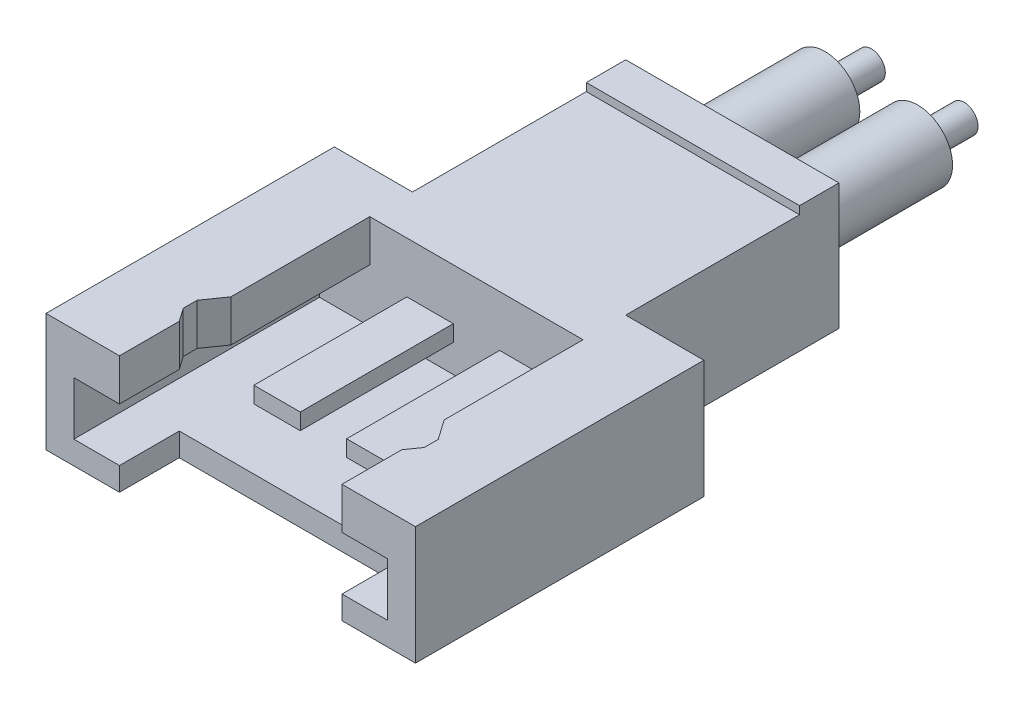
SolidWorks part; units mm, degrees
ref_plane "Front Plane" through (0, 0, 0) normal (0, 0, 1) x (1, 0, 0)
ref_plane "Top Plane" through (0, 0, 0) normal (0, 1, 0) x (1, 0, 0)
ref_plane "Right Plane" through (0, 0, 0) normal (1, 0, 0) x (0, 0, -1)
sketch "Sketch1" plane through (0, 0, 0) normal (0, 0, 1) x (1, 0, 0)
  line L1 (-2.3, 1.275) -> (2.3, 1.275)
  line L2 (-2.3, 1.275) -> (-2.3, -1.275)
  line L3 (-2.3, -1.275) -> (2.3, -1.275)
  line L4 (2.3, 1.275) -> (2.3, -1.275)
  line L5 (-2.3, 1.275) -> (2.3, -1.275) construction
  line L6 (-2.3, -1.275) -> (2.3, 1.275) construction
  point P0 (0, 0)
  dimension "D1" = 4.6
  dimension "D2" = 2.55
extrude "Boss-Extrude1" add sketch "Sketch1" along normal blind 4.6
sketch "Sketch2" plane through (0, 0, 4.6) normal (0, 0, 1) x (1, 0, 0)
  line L0 (2.3, 1.275) -> (-2.3, 1.275) construction
  line L1 (-3.985, 1.275) -> (3.985, 1.275)
  line L2 (-3.985, 1.275) -> (-3.985, -1.275)
  line L3 (-3.985, -1.275) -> (3.985, -1.275)
  line L4 (3.985, 1.275) -> (3.985, -1.275)
  line L5 (-3.985, 1.275) -> (3.985, -1.275) construction
  line L6 (-3.985, -1.275) -> (3.985, 1.275) construction
  point P0 (0, 0)
  dimension "D1" = 7.97
extrude "Boss-Extrude2" add sketch "Sketch2" along normal blind 6.22
sketch "Sketch3" plane through (0, 1.275, 0) normal (0, 1, 0) x (1, 0, 0)
  line L0 (2.3, -4.6) -> (2.3, 0) construction
  line L1 (-2.3, 0) -> (2.3, 0)
  line L2 (-2.3, 0) -> (-2.3, -0.85)
  line L3 (-2.3, -0.85) -> (2.3, -0.85)
  line L4 (2.3, 0) -> (2.3, -0.85)
  dimension "D1" = 0.85
extrude "Boss-Extrude3" add sketch "Sketch3" along normal offset from surface (0.17 mm away) 2.72 up to face at (0, -1.275, 5.005)
sketch "Sketch4" plane through (0, 0, 10.82) normal (0, 0, 1) x (1, 0, 0)
  line L0 (-3.985, -1.275) -> (3.985, -1.275) construction
  line L1 (-2.4, 1.275) -> (2.4, 1.275)
  line L2 (-2.4, 1.275) -> (-2.4, -1.275)
  line L3 (-2.4, -1.275) -> (2.4, -1.275)
  line L4 (2.4, 1.275) -> (2.4, -1.275)
  line L5 (-2.4, 1.275) -> (2.4, -1.275) construction
  line L6 (-2.4, -1.275) -> (2.4, 1.275) construction
  point P0 (0, 0)
  dimension "D1" = 4.8
extrude "Cut-Extrude1" cut sketch "Sketch4" against normal blind 1.29
sketch "Sketch5" plane through (0, 0, 10.82) normal (0, 0, 1) x (1, 0, 0)
  line L0 (0, 1.275) -> (0, -1.275) construction
  line L1 (-2.3, 1.275) -> (2.3, 1.275) construction
  line L2 (-2.4, -1.275) -> (2.4, -1.275) construction
  line L3 (-3.985, -1.275) -> (-2.4, -1.275) construction
  line L4 (-3.385, 0.375) -> (3.385, 0.375)
  line L5 (-3.385, 0.375) -> (-3.385, -0.775)
  line L6 (-3.385, -0.775) -> (3.385, -0.775)
  line L7 (3.385, 0.375) -> (3.385, -0.775)
  line L8 (-3.385, 0.375) -> (3.385, -0.775) construction
  line L9 (-3.385, -0.775) -> (3.385, 0.375) construction
  line L10 (-3.985, 1.275) -> (-3.985, -1.275) construction
  line L11 (-2.4, 1.275) -> (-3.985, 1.275) construction
  point P6 (0, -0.2)
  dimension "D1" = 0.5
  dimension "D2" = 0.6
  dimension "D3" = 0.9
extrude "Cut-Extrude2" cut sketch "Sketch5" against normal blind 5.3
sketch "Sketch6" plane through (0, 1.275, 0) normal (0, 1, 0) x (1, 0, 0)
  line L0 (0, -0.85) -> (0, -9.53) construction
  line L1 (-2.3, -0.85) -> (2.3, -0.85) construction
  line L2 (2.4, -9.53) -> (-2.4, -9.53) construction
  line L3 (-3.385, -5.52) -> (3.385, -5.52) construction
  line L4 (2.3, -5.52) -> (-2.3, -5.52)
  line L5 (2.3, -5.52) -> (2.3, -9.53)
  line L6 (2.3, -9.53) -> (-2.3, -9.53)
  line L7 (-2.3, -5.52) -> (-2.3, -9.53)
  line L8 (2.3, -5.52) -> (-2.3, -9.53) construction
  line L9 (2.3, -9.53) -> (-2.3, -5.52) construction
  line L10 (-2.4, -9.53) -> (-2.6, -9.2444)
  line L11 (-2.6, -9.2444) -> (-2.6, -8.9444)
  line L12 (-2.6, -8.9444) -> (-2.3, -8.5159)
  line L13 (-2.6, -9.0944) -> (-2.3, -9.0944) construction
  line L14 (-2.4, -9.53) -> (-2.3, -9.53)
  line L15 (2.6, -8.9444) -> (2.3, -8.5159)
  line L16 (2.6, -9.2444) -> (2.6, -8.9444)
  line L17 (2.4, -9.53) -> (2.6, -9.2444)
  line L18 (2.4, -9.53) -> (2.3, -9.53)
  point P6 (0, -7.525)
  line M3 (-2.4, -9.53) -> (2.4, -9.53)
  dimension "D1" = 4.6
  dimension "D2" = 0.3
  dimension "D3" = 145
  dimension "D4" = 0.3
extrude "Cut-Extrude3" cut sketch "Sketch6" against normal up to next contours L4 L7 L5 M3 | L12 L11 L10 L7 M3 | L17 L16 L15 L5 M3 region at (0, 1.275, 7.525) region at (2.4235, 1.275, 9.078) region at (-2.4235, 1.275, 9.078)
sketch "Sketch7" plane through (0, 0, 5.52) normal (0, 0, 1) x (1, 0, 0)
  line L0 (-3.985, 0) -> (3.985, 0) construction
  line L1 (-3.985, 1.275) -> (-3.985, -1.275) construction
  line L2 (3.985, -1.275) -> (3.985, 1.275) construction
  line L3 (0, 1.445) -> (0, -1.275) construction
  line L4 (-2.3, 1.445) -> (2.3, 1.445) construction
  line L5 (-2.4, -1.275) -> (2.4, -1.275) construction
  line L6 (1.5, 0.175) -> (1.5, -0.175)
  line L7 (-1.5, 0.175) -> (-0.5, 0.175)
  line L8 (-1.5, 0.175) -> (-1.5, -0.175)
  line L9 (-1.5, -0.175) -> (-0.5, -0.175)
  line L10 (-0.5, 0.175) -> (-0.5, -0.175)
  line L11 (-1.5, 0.175) -> (-0.5, -0.175) construction
  line L12 (-1.5, -0.175) -> (-0.5, 0.175) construction
  line L13 (1.5, 0.175) -> (0.5, 0.175)
  line L14 (0.5, 0.175) -> (0.5, -0.175)
  line L15 (1.5, -0.175) -> (0.5, -0.175)
  point P12 (-1, 0)
  dimension "D1" = 0.35
  dimension "D2" = 1
  dimension "D3" = 2
extrude "Boss-Extrude4" add sketch "Sketch7" along normal offset from surface (3.3 mm away) 2 up to face at (-3.0425, -0.1, 10.82)
sketch "Sketch8" plane through (0, 0, 0) normal (0, 0, -1) x (-1, 0, 0)
  line L0 (-3.985, 0) -> (3.985, 0) construction
  line L1 (-3.985, -1.275) -> (-3.985, 1.275) construction
  line L2 (3.985, 1.275) -> (3.985, -1.275) construction
  line L3 (0, 1.445) -> (0, -1.275) construction
  line L4 (-2.3, 1.445) -> (2.3, 1.445) construction
  line L5 (2.3, -1.275) -> (-2.3, -1.275) construction
  circle A0 centre (-1, 0) radius 0.75
  circle A1 centre (1, 0) radius 0.75
  dimension "D2" = 1.5
  dimension "D1" = 2
extrude "Boss-Extrude5" add sketch "Sketch8" along normal blind 3
sketch "Sketch9" plane through (0, 0, -3) normal (0, 0, -1) x (-1, 0, 0)
  circle A0 centre (-1, 0) radius 0.3
  circle A1 centre (1, 0) radius 0.3
  dimension "D1" = 0.6
extrude "Boss-Extrude6" add sketch "Sketch9" along normal blind 1
